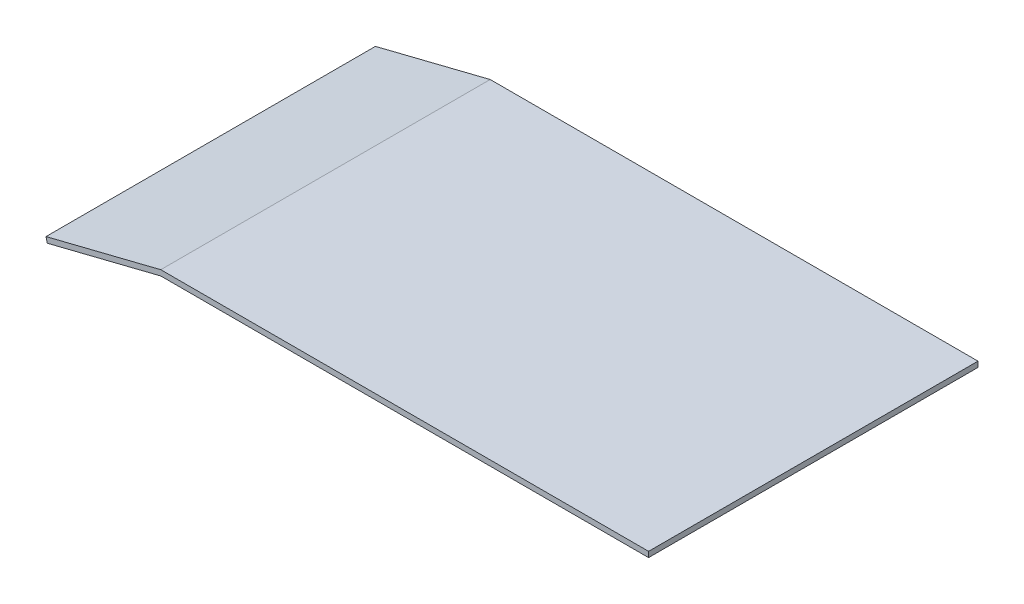
SolidWorks part; units mm, degrees
material "5052-H32"
ref_plane "Front Plane" through (0, 0, 0) normal (0, 0, 1) x (1, 0, 0)
ref_plane "Top Plane" through (0, 0, 0) normal (0, 1, 0) x (1, 0, 0)
ref_plane "Right Plane" through (0, 0, 0) normal (1, 0, 0) x (0, 0, -1)
sketch "Sketch1" plane through (0, 0, 0) normal (0, 0, 1) x (1, 0, 0)
  line L0 (-461.865, 4.4417) -> (-36.865, 4.4417)
  line L1 (-36.865, 4.4417) -> (-36.865, -0.3208)
  line L2 (-561.865, -20.5583) -> (-461.865, 4.4417)
  line L3 (-36.865, -0.3208) -> (-461.865, -0.3208)
  line L4 (-461.865, -0.3208) -> (-560.7444, -25.0407)
  line L5 (-560.7444, -25.0407) -> (-561.865, -20.5583)
  point P2 (-461.865, 4.4417)
extrude "Boss-Extrude1" add sketch "Sketch1" along normal blind 287
